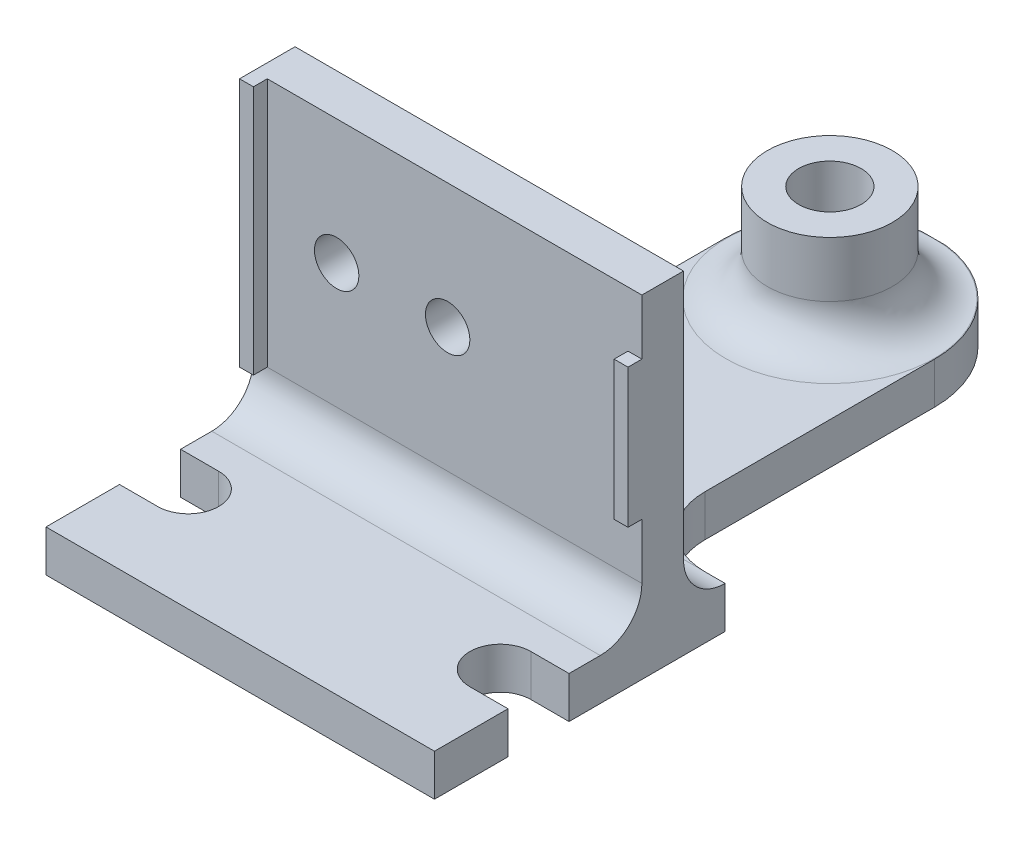
SolidWorks part; units mm, degrees
ref_plane "Front Plane" through (0, 0, 0) normal (0, 0, 1) x (1, 0, 0)
ref_plane "Top Plane" through (0, 0, 0) normal (0, 1, 0) x (1, 0, 0)
ref_plane "Right Plane" through (0, 0, 0) normal (1, 0, 0) x (0, 0, -1)
sketch "Sketch2" plane through (0, 0, 0) normal (0, 1, 0) x (1, 0, 0)
  line L1 (0, 0) -> (28, 0)
  line L2 (0, 0) -> (0, 50)
  line L3 (0, 50) -> (28, 50)
  line L4 (28, 0) -> (28, 50)
extrude "Boss-Extrude1" add sketch "Sketch2" along normal blind 24
sketch "Sketch3" plane through (0, 24, 0) normal (0, 1, 0) x (1, 0, 0)
  line L1 (0, -0.0499) -> (28, -0.0499)
  line L24 (28, 50) -> (0, 50)
  line L26 (1, 14.9501) -> (27, 14.9501)
  line L27 (27, 14.9501) -> (27, 13.9501)
  line L28 (27, 13.9501) -> (28, 13.9501)
  line L29 (1, 14.9501) -> (1, 13.9501)
  line L30 (1, 13.9501) -> (0, 13.9501)
  line L31 (0, 13.9501) -> (0, -0.0499)
  line L32 (28, 13.9501) -> (28, -0.0499)
  line L37 (0, 17.9501) -> (28, 17.9501)
  line L38 (0, 50) -> (0, 0) construction
  line L39 (28, 0) -> (28, 50) construction
  line L40 (0, 50) -> (0, 17.9501)
  line L41 (28, 50) -> (28, 17.9501)
  circle A0 centre (14, 42.5) radius 4.5
extrude "Cut-Extrude1" cut sketch "Sketch3" against normal offset from surface (21 mm away) 3 up to face at (14, 0, -25)
sketch "Sketch4" plane through (0, 0, -13.9501) normal (0, 0, 1) x (1, 0, 0)
  line L1 (0, 3) -> (1, 3)
  line L2 (0, 3) -> (0, 6)
  line L3 (0, 6) -> (1, 6)
  line L4 (1, 3) -> (1, 6)
  line L6 (27, 3) -> (28, 3)
  line L7 (27, 3) -> (27, 10)
  line L8 (27, 10) -> (28, 10)
  line L9 (28, 3) -> (28, 10)
  line L11 (27, 24) -> (28, 24)
  line L12 (27, 24) -> (27, 20)
  line L13 (27, 20) -> (28, 20)
  line L14 (28, 24) -> (28, 20)
extrude "Cut-Extrude2" cut sketch "Sketch4" against normal up to surface (1 mm away) up to face at (14, 13.5, -14.9501)
fillet "Fillet2" radius 3 3 edges at (14, 3, -14.9501) (14, 3, -17.9501) (14, 3, -47)
sketch "Sketch5" plane through (0, 24, 0) normal (0, 1, 0) x (1, 0, 0)
  line L1 (6.45, 42.5) -> (6.45, 25.9501)
  line L10 (2.75, 9.7) -> (0, 9.7)
  line L11 (21.55, 42.5) -> (21.55, 25.9501)
  line L13 (2.75, 5.3) -> (0, 5.3)
  line L14 (0, 5.3) -> (0, 9.7)
  line L15 (25.25, 9.7) -> (28, 9.7)
  line L17 (25.25, 5.3) -> (28, 5.3)
  line L18 (28, 5.3) -> (28, 9.7)
  line L19 (13.1325, 50) -> (0, 50)
  line L20 (14, 50) -> (0, 50) construction
  line L21 (0, 50) -> (0, 20.9501)
  line L22 (0, 20.9501) -> (1.45, 20.9501)
  line L23 (28, 20.9501) -> (28, 50)
  line L24 (28, 50) -> (14.8675, 50)
  line L26 (26.55, 20.9501) -> (28, 20.9501)
  circle A4 centre (14, 42.5) radius 2.25
  arc A5 (25.25, 9.7) -> (25.25, 5.3) centre (25.25, 7.5) ccw
  arc A6 (2.75, 5.3) -> (2.75, 9.7) centre (2.75, 7.5) ccw
  arc A8 (21.55, 42.5) -> (14.8675, 50) centre (14, 42.5) ccw
  arc A9 (13.1325, 50) -> (6.45, 42.5) centre (14, 42.5) ccw
  arc A10 (21.55, 25.9501) -> (26.55, 20.9501) centre (26.55, 25.9501) ccw
  arc A11 (6.45, 25.9501) -> (1.45, 20.9501) centre (1.45, 25.9501) cw
  dimension "D1" = 5
extrude "Cut-Extrude3" cut sketch "Sketch5" against normal up to surface (24 mm away) up to face at (14, 0, -25)
sketch "Sketch6" plane through (0, 0, -14.9501) normal (0, 0, 1) x (1, 0, 0)
  circle A0 centre (6, 15) radius 1.6
  circle A1 centre (14, 15) radius 1.6
extrude "Cut-Extrude4" cut sketch "Sketch6" against normal up to surface (3 mm away) up to face at (14, 15, -17.9501)
sketch "Sketch8" plane through (0, 24, 0) normal (0, 1, 0) x (1, 0, 0)
  circle A0 centre (14, 42.5) radius 4.5
extrude "Cut-Extrude6" cut sketch "Sketch8" against normal offset from surface (14 mm away) 10 up to face at (14, 0, -44.75)
